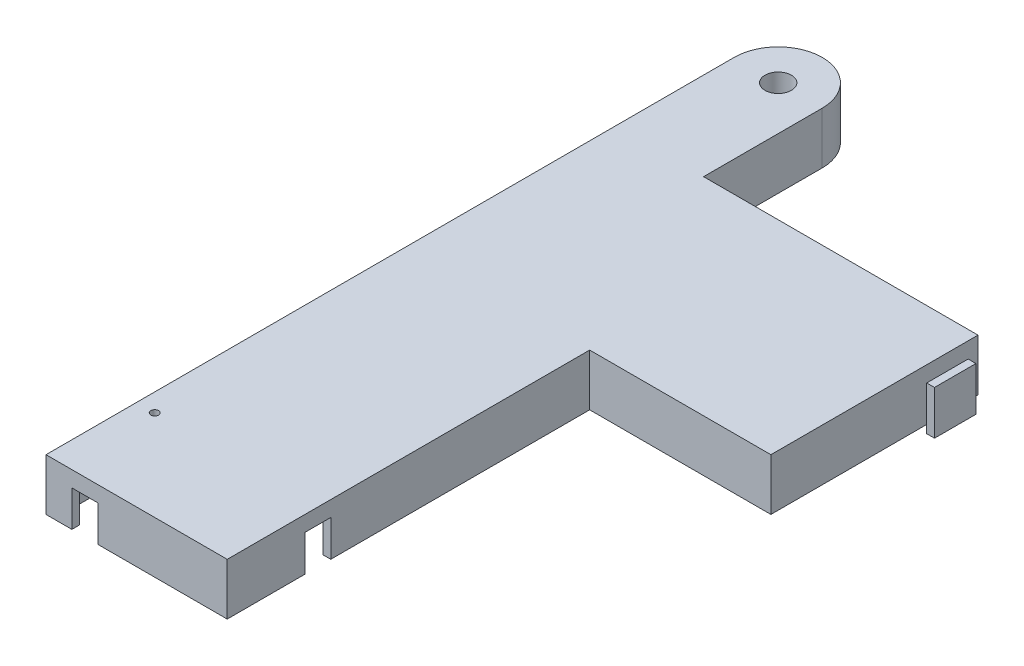
SolidWorks part; units mm, degrees
ref_plane "Front Plane" through (0, 0, 0) normal (0, 0, 1) x (1, 0, 0)
ref_plane "Top Plane" through (0, 0, 0) normal (0, 1, 0) x (1, 0, 0)
ref_plane "Right Plane" through (0, 0, 0) normal (1, 0, 0) x (0, 0, -1)
sketch "CornerrSketch1" plane through (0, 0, 0) normal (0, 1, 0) x (1, 0, 0)
  line L0 (140, 220) -> (140, 140)
  line L2 (0, 0) -> (0, 265.825)
  line L5 (140, 140) -> (70, 140)
  line L6 (70, 140) -> (70, 0)
  line L7 (0, 0) -> (70, 0)
  line L9 (34, 265.825) -> (34, 220)
  line L10 (34, 220) -> (140, 220)
  arc A0 (34, 265.825) -> (0, 265.825) centre (17, 265.825) ccw
  point P2 (17, 282.825)
  point P8 (0, 132.9125)
  dimension "D3" = 34
  dimension "D4" = 80
  dimension "D1" = 220
  dimension "D5" = 45.825
  dimension "D6" = 282.825
  dimension "D7" = 140
  dimension "D11" = 70
extrude "CornerBoss-Extrude1" add sketch "CornerrSketch1" along normal blind 20
shell "Shell2" thickness 3 removed face at (61, 0, -158.5813)
sketch "PadSketch3" plane through (0, 17, 0) normal (0, -1, 0) x (1, 0, 0)
  line L0 (0, -265.825) -> (0, 0) construction
  line L1 (140, -220) -> (34, -220) construction
  circle A0 centre (17, -265.825) radius 12
  circle A1 centre (7, -35) radius 5
  dimension "D1" = 24
  dimension "D2" = 10
  dimension "D3" = 7
  dimension "D4" = 185
extrude "PadBoss-Extrude2" add sketch "PadSketch3" along normal blind 10
sketch "StepperShaftHoleSketch4" plane through (0, 7, 0) normal (0, -1, 0) x (1, 0, 0)
  circle A0 centre (17, -265.825) radius 5.1
  circle A1 centre (7, -35) radius 1.5
  dimension "D2" = 3
  dimension "D1" = 10.2
extrude "StepperShaftCut-Extrude2" cut sketch "StepperShaftHoleSketch4" against normal through all
sketch "ThreadedNutMountHolesSketch5" plane through (0, 7, 0) normal (0, -1, 0) x (-1, 0, 0)
  circle A8 centre (-17, 273.825) radius 1
  circle A9 centre (-9, 265.825) radius 1
  circle A10 centre (-17, 257.825) radius 1
  circle A11 centre (-25, 265.825) radius 1
  dimension "D1" = 2
  dimension "D2" = 8
  dimension "D3" = 16
  dimension "D5" = 16
extrude "ThreadedNutMountHolesCut-Extrude4" cut sketch "ThreadedNutMountHolesSketch5" against normal blind 10
sketch "TRPegSketch1" plane through (140, 0, 0) normal (1, 0, 0) x (0, 0, -1)
  line L0 (220, 20) -> (220, 0) construction
  line L1 (200.1, 13.9) -> (209.9, 13.9)
  line L2 (200.1, 13.9) -> (200.1, 0)
  line L3 (200.1, 0) -> (209.9, 0)
  line L4 (209.9, 13.9) -> (209.9, 0)
  line L5 (140, 0) -> (220, 0) construction
  point P6 (220, 10)
  dimension "D1" = 10.1
  dimension "D2" = 13.9
  dimension "D3" = 9.8
extrude "TRPegBoss-Extrude1" add sketch "TRPegSketch1" along normal blind 3.1
sketch "TRPegCapSketch2" plane through (143.1, 0, 0) normal (1, 0, 0) x (0, 0, -1)
  line L0 (200.1, 0) -> (209.9, 0) construction
  line L1 (197.1, 17) -> (213.1, 17)
  line L2 (197.1, 17) -> (197.1, 0)
  line L3 (197.1, 0) -> (213.1, 0)
  line L4 (213.1, 17) -> (213.1, 0)
  line L5 (200.1, 13.9) -> (200.1, 0) construction
  dimension "D1" = 16
  dimension "D2" = 3
  dimension "D3" = 17
extrude "TRPegCapBoss-Extrude2" add sketch "TRPegCapSketch2" along normal blind 3
sketch "BottomPegHoleSketch3" plane through (0, 0, 0) normal (0, 0, 1) x (1, 0, 0)
  line L0 (0, 0) -> (70, 0) construction
  line L1 (10, 13.9) -> (20, 13.9)
  line L2 (10, 13.9) -> (10, 0)
  line L3 (10, 0) -> (20, 0)
  line L4 (20, 13.9) -> (20, 0)
  line L5 (0, 20) -> (0, 0) construction
  line L6 (143.1, 13.9) -> (140, 13.9) construction
  dimension "D2" = 10
  dimension "D3" = 10
extrude "BottomPegHoleCut-Extrude1" cut sketch "BottomPegHoleSketch3" against normal blind 3
sketch "BedCenterPegHoleCutSketch1" plane through (70, 0, 0) normal (1, 0, 0) x (0, 0, -1)
  line L0 (0, 0) -> (140, 0) construction
  line L1 (30, 14) -> (40, 14)
  line L2 (30, 14) -> (30, 0)
  line L3 (30, 0) -> (40, 0)
  line L4 (40, 14) -> (40, 0)
  line L5 (140, 20) -> (140, 0) construction
  dimension "D2" = 10
  dimension "D1" = 14
  dimension "D3" = 100
extrude "BedCenterPegHoleCut-Extrude1" cut sketch "BedCenterPegHoleCutSketch1" against normal blind 3
equation "\"RailThickness\"= .125in'Spec"
equation "\"StepperMountingHoleDistance\"= 31mm'Spec"
equation "\"StepperMountingHoleOffsetFromLeftOrRightSide\"= \"StepperMountingHoleOffsetFromItsSide\" + \"RailThickness\""
equation "\"StepperMountingHoleOffsetFromItsSide\"= 5.5mm'Spec"
equation "\"FrontBackRailLength\"= 510mm"
equation "\"DistanceBetweenLeftToRightStepperHoles\"= \"FrontBackRailLength\" - \"StepperMountingHoleOffsetFromLeftOrRightSide\" * 2 - \"StepperMountingHoleDistance\"'Equals 461.65"
equation "\"BedThickness\"= 20mm"
equation "\"BedToBuildPlateStandoffHoleSize\"= 3mm"
equation "\"BedLLongSide\"= \"BedThirdSize\" * 3'Equals 210"
equation "\"BedLShortSide\"= \"BedThirdSize\" * 2'Equals 140"
equation "\"BedLWidth\"= \"BedThirdSize\"'Equals 70"
equation "\"D4@CornerrSketch1\"=\"BedLWidth\" + \"BedIncreasedByWidth\"/2"
equation "\"D1@CornerrSketch1\" = \"BedLLongSide\" + \"BedIncreasedByWidth\" / 2"
equation "\"BedInnerSquareWidth\"= \"BedThirdSize\" * 3'Equals 210"
equation "\"BedWidth\"= \"BedInnerSquareWidth\" + \"BedLWidth\" * 2 + \"BedIncreasedByWidth\"'Equals 370"
equation "\"BedIncreasedByWidth\"= 20mm"
equation "\"BedIncreasedByLength\"= 0mm"
equation "\"BedThirdSize\"= 70mm"
equation "\"D1@TRPegCapSketch2\"=\"BedPegCapWidth\""
equation "\"StandardWallThickness\"= 3mm"
equation "\"D2@TRPegCapSketch2\" = \"StandardWallThickness\""
equation "\"D3@TRPegCapSketch2\"=\"BedPegCapHeight\""
equation "\"D1@TRPegCapBoss-Extrude2\" = \"StandardWallThickness\""
equation "\"D1@BottomPegHoleCut-Extrude1\"=\"StandardWallThickness\""
equation "\"D1@Shell2\"=\"StandardWallThickness\""
equation "\"D2@TRPegSketch1\"=\"BedPegHeight\""
equation "\"D5@CornerrSketch1\"=\"DistanceFromBedSideToStepperHole\""
equation "\"DistanceFromBedFrontToStepperHole\"= \"LeadScrewNutPadSize\" + 10mm"
equation "\"DistanceFromBedSideToStepperHole\"= ( \"DistanceBetweenLeftToRightStepperHoles\" - \"BedWidth\" ) / 2'Equals 45.825"
equation "\"D7@CornerrSketch1\"= \"BedLShortSide\" + \"BedIncreasedByLength\" / 2"
equation "\"D3@CornerrSketch1\"=\"DistanceFromBedFrontToStepperHole\""
equation "\"BedToBuildPlateStandoffPadSize\"= 10mm"
equation "\"LeadScrewNutPadSize\"= \"LeadScrewNutMountingHoleFlangeDiameter\" + 2mm'Equals 24"
equation "\"D1@PadSketch3\" = \"LeadScrewNutPadSize\""
equation "\"D1@StepperShaftHoleSketch4\"=\"LeadScrewNutInnerShaftFlangeDiameter\""
equation "\"D11@CornerrSketch1\"=\"BedLWidth\""
equation "\"LeadScrewNutInnerShaftFlangeDiameter\"= 10.2mm'Spec"
equation "\"LeadScrewNutMountHoleDiameter\"= 2mm'Spec is 4.1 but smaller for tapping"
equation "\"LeadScrewNutMountingHoleFlangeDiameter\"= 22mm'Spec"
equation "\"LeadScrewNutMountingHoleDistance\"= 16mm'Spec"
equation "\"D2@ThreadedNutMountHolesSketch5\"=\"LeadScrewNutMountingHoleDistance\" / 2"
equation "\"D3@ThreadedNutMountHolesSketch5\"=\"LeadScrewNutMountingHoleDistance\""
equation "\"D5@ThreadedNutMountHolesSketch5\"=\"LeadScrewNutMountingHoleDistance\""
equation "\"D4@ThreadedNutMountHolesSketch5\"=\"LeadScrewNutMountingHoleDistance\"/2"
equation "\"D1@ThreadedNutMountHolesSketch5\"=\"LeadScrewNutMountHoleDiameter\""
equation "\"LeadScrewNutPadDepth\"= \"BedThickness\" / 2'Equals 10"
equation "\"D1@ThreadedNutMountHolesCut-Extrude4\"=\"LeadScrewNutPadDepth\""
equation "\"D2@PadSketch3\"=\"BedToBuildPlateStandoffPadSize\""
equation "\"D3@PadSketch3\"=\"BedToBuildPlateStandoffHolesDistanceFromFront\""
equation "\"BuildPlateWidth\"= 350mm'Spec"
equation "\"D4@PadSketch3\"=\"BedIncreasedByWidth\"/2 + \"BuildPlateWidth\"/2"
equation "\"D2@StepperShaftHoleSketch4\"=\"BedToBuildPlateStandoffHoleSize\""
equation "\"BuildPlateStandoffHolesDistanceFromFront\"= 7mm"
equation "\"BedToBuildPlateStandoffHolesDistanceFromFront\"= \"BuildPlateStandoffHolesDistanceFromFront\" + \"BedIncreasedByLength\" / 2'Equals 7"
equation "\"BedPegHoleWidth\"= 10mm"
equation "\"BedPegHoleHeight\"= \"BedThickness\" - \"StandardWallThickness\" * 2'Equals 14"
equation "\"BedPegWidth\"= \"BedPegHoleWidth\" - .1mm * 2'For easier assembly"
equation "\"BedPegHeight\"= \"BedPegHoleHeight\" - .1mm'For easier assembly"
equation "\"BedTopPegOffsetFromSide\"= 10mm"
equation "\"BedPegBoss\"= \"StandardWallThickness\" + .1mm'For easier assembly"
equation "\"BedPegCapHeight\"= \"BedThickness\" - \"StandardWallThickness\"'Equals 17"
equation "\"BedPegCapWidth\"= \"BedThickness\" / 2 + \"StandardWallThickness\" * 2'Equals 16"
equation "\"D1@TRPegSketch1\"=\"BedTopPegOffsetFromSide\" + .1mm"
equation "\"D3@TRPegSketch1\"= \"BedPegWidth\""
equation "\"D1@TRPegBoss-Extrude1\"=\"BedPegBoss\""
equation "\"D3@BottomPegHoleSketch3\"=\"BedTopPegOffsetFromSide\""
equation "\"D2@BottomPegHoleSketch3\"=\"BedPegHoleWidth\""
equation "\"D1@BedCenterPegHoleCutSketch1\" = \"BedPegHoleHeight\""
equation "\"D2@BedCenterPegHoleCutSketch1\" = \"BedPegHoleWidth\""
equation "\"D3@BedCenterPegHoleCutSketch1\" = \"BedInnerSquareWidth\" / 2 - \"BedPegHoleWidth\" / 2"
equation "\"D1@BedCenterPegHoleCut-Extrude1\"=\"StandardWallThickness\""
